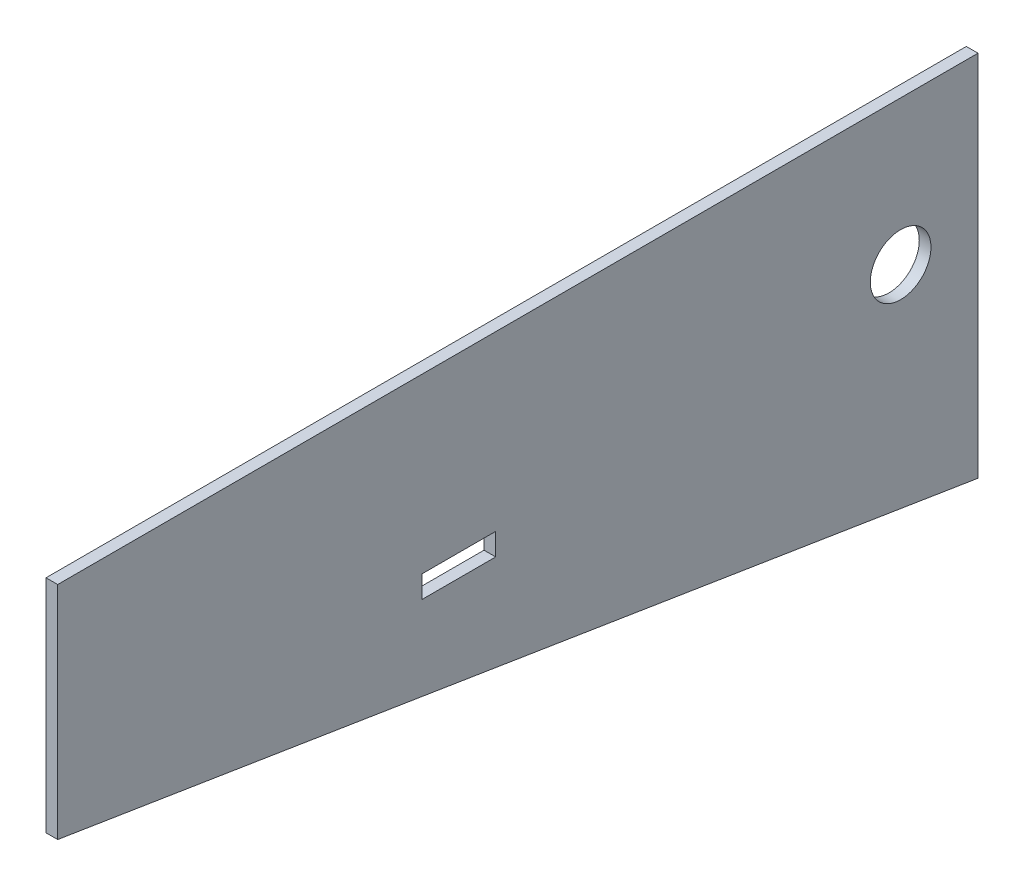
SolidWorks part; units mm, degrees
ref_plane "Front Plane" through (0, 0, 0) normal (0, 0, 1) x (1, 0, 0)
ref_plane "Top Plane" through (0, 0, 0) normal (0, 1, 0) x (1, 0, 0)
ref_plane "Right Plane" through (0, 0, 0) normal (1, 0, 0) x (0, 0, -1)
sketch "Sketch1" plane through (0, 0, 0) normal (1, 0, 0) x (0, 0, -1)
  line L0 (0, 17.8493) -> (0, 30)
  line L1 (0, 0) -> (0, 4.4613)
  line L2 (0, 4.4613) -> (0, 9.4613)
  line L3 (0, 9.4613) -> (0, 17.8493)
  line L4 (0, 30) -> (125, 30)
  line L5 (125, 30) -> (125, -20)
  line L6 (125, -20) -> (0, 0)
  point P7 (0, 0)
  dimension "D1" = 30
  dimension "D2" = 125
  dimension "D3" = 125
  dimension "D4" = 50
extrude "Boss-Extrude1" add sketch "Sketch1" along normal blind 1.5875 contours L4 L5 L6 L1 L2 L3 L0
sketch "Sketch2" plane through (1.5875, 0, 0) normal (1, 0, 0) x (0, 0, -1)
  line L0 (0, 30) -> (125, 30) construction
  line L1 (125, 30) -> (125, -20) construction
  line L3 (49.49, 6.51) -> (59.49, 6.51)
  line L4 (49.49, 6.51) -> (49.49, 3.5)
  line L5 (49.49, 3.5) -> (59.49, 3.5)
  line L6 (59.49, 6.51) -> (59.49, 3.5)
  line L7 (49.49, 6.51) -> (59.49, 3.5) construction
  line L8 (49.49, 3.5) -> (59.49, 6.51) construction
  circle A0 centre (114.49, 10.38) radius 4.12
  point P2 (0, 0)
  point P7 (54.49, 5.005)
  point P12 (59.49, 5.005)
  dimension "D3" = 8.24
  dimension "D1" = 19.62
  dimension "D2" = 10.51
  dimension "D4" = 55
  dimension "D5" = 10
  dimension "D6" = 3.01
  dimension "D7" = 23.49
extrude "Cut-Extrude1" cut sketch "Sketch2" against normal blind 1.5875
